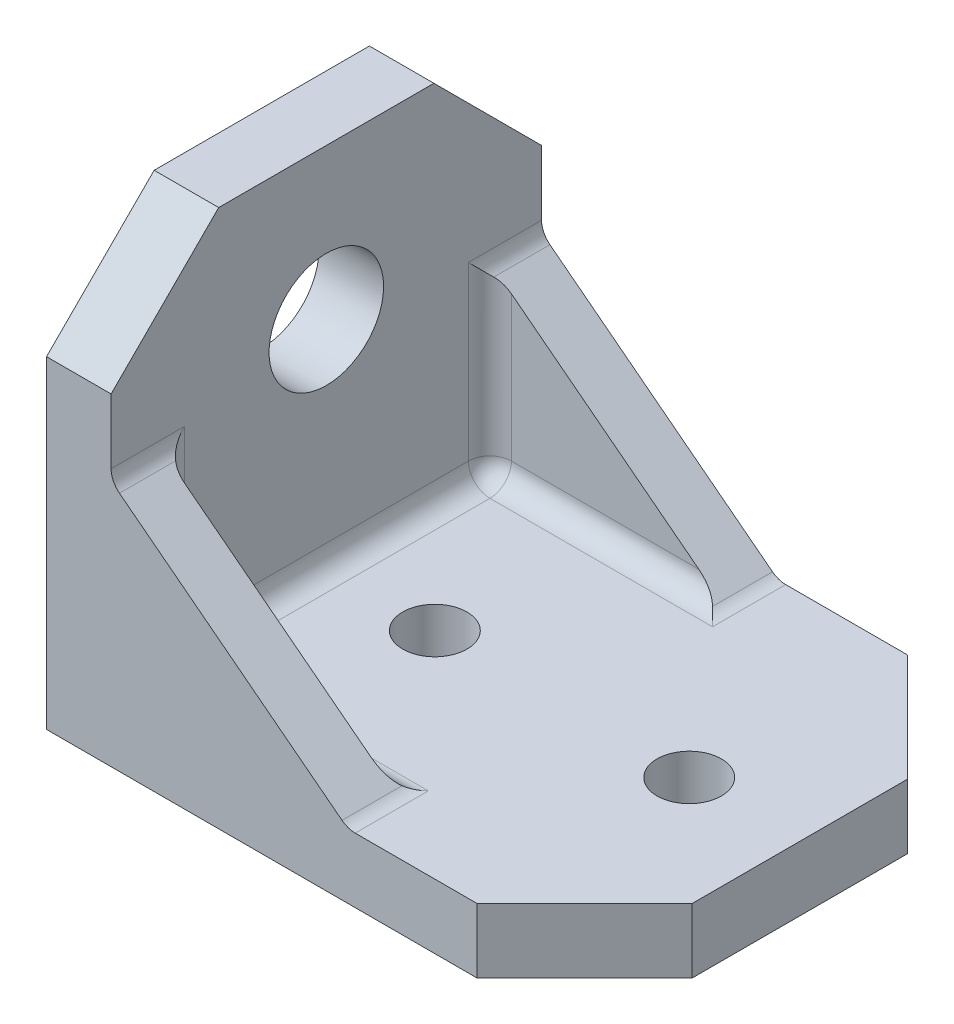
SolidWorks part; units mm, degrees
material "ABS"
ref_plane "Front" through (0, 0, 0) normal (0, 0, 1) x (1, 0, 0)
ref_plane "Top" through (0, 0, 0) normal (0, 1, 0) x (1, 0, 0)
ref_plane "Right" through (0, 0, 0) normal (1, 0, 0) x (0, 0, -1)
ref_axis "Axis1" through (0, 0, 55) along (0, 0, -1)
sketch "Sketch1" plane through (0, 0, 0) normal (0, 0, 1) x (1, 0, 0)
  line L0 (0, 0) -> (0, 25.4)
  line L1 (0, 0) -> (31.75, 0)
  line L2 (3.81, 3.81) -> (31.75, 3.81)
  line L3 (3.81, 3.81) -> (3.81, 25.4)
  line L4 (0, 25.4) -> (3.81, 25.4)
  line L5 (31.75, 3.81) -> (31.75, 0)
  dimension "D2" = 25.4
  dimension "D3" = 31.75
  dimension "D1" = 3.81
extrude "Boss-Extrude1" add sketch "Sketch1" along normal blind 25.4
hole_wizard "#6 Clearance Hole1" positions "Sketch2" profile "Sketch3" hole size "#6" standard "ANSI Inch" end condition through all
sketch "Sketch2" plane through (0, 3.81, 0) normal (0, 1, 0) x (1, 0, 0)
  line L0 (3.81, -12.7) -> (31.75, -12.7) construction
  line L1 (3.81, -25.4) -> (3.81, 0) construction
  line L2 (31.75, -25.4) -> (31.75, 0) construction
  line L4 (0, -25.4) -> (0, 0) construction
  point P0 (10.2108, -12.7)
  point P2 (25.2222, -12.7)
  point P12 (25.6439, -12.7)
  point P13 (11.4084, -12.7)
  dimension "D1" = 15.0114
  dimension "D2" = 10.2108
sketch "Sketch3" plane through (10.2108, 3.81, 12.7) normal (1, 0, 0) x (0, 0, 1)
  line L0 (0, 0) -> (0, 3.81)
  line L1 (0, 3.81) -> (1.8986, 3.81)
  line L2 (1.8986, 3.81) -> (1.8986, 0)
  line L5 (1.8986, 0) -> (0, 0)
  line L11 (0, -6.35) -> (0, 107.95) construction
  dimension "Thru Hole Dia." = 3.7973
  dimension "Thru Hole Depth" = 3.81
hole_wizard "1/4 Clearance Hole1" positions "Sketch4" profile "Sketch5" hole size "1/4" standard "ANSI Inch" end condition through all
sketch "Sketch4" plane through (3.81, 0, 0) normal (1, 0, 0) x (0, 0, -1)
  line L0 (-12.7, 25.4) -> (-12.7, 3.81) construction
  line L1 (-25.4, 25.4) -> (0, 25.4) construction
  line L2 (-25.4, 3.81) -> (0, 3.81) construction
  point P0 (-12.7, 16.51)
  point P10 (-12.7, 16.6994)
  dimension "D1" = 8.89
sketch "Sketch5" plane through (3.81, 16.51, 12.7) normal (0, 1, 0) x (0, 0, -1)
  line L0 (0, 0) -> (0, 3.81)
  line L1 (0, 3.81) -> (3.3782, 3.81)
  line L2 (3.3782, 3.81) -> (3.3782, 0)
  line L5 (3.3782, 0) -> (0, 0)
  line L11 (0, -6.35) -> (0, 107.95) construction
  dimension "Thru Hole Dia." = 6.7564
  dimension "Thru Hole Depth" = 3.81
sketch "Sketch6" plane through (0, 0, 25.4) normal (0, 0, 1) x (1, 0, 0)
  line L0 (3.81, 3.81) -> (17.78, 3.81)
  line L1 (31.75, 3.81) -> (3.81, 3.81) construction
  line L2 (17.78, 3.81) -> (3.81, 14.605)
  line L3 (3.81, 3.81) -> (3.81, 25.4) construction
  line L4 (3.81, 14.605) -> (3.81, 3.81)
extrude "Boss-Extrude2" add sketch "Sketch6" against normal blind 3.048
sketch "Sketch7" plane through (0, 0, 0) normal (0, 0, -1) x (-1, 0, 0)
  line L0 (-3.81, 3.81) -> (-17.78, 3.81)
  line L1 (-31.75, 3.81) -> (-3.81, 3.81) construction
  line L2 (-17.78, 3.81) -> (-3.81, 14.605)
  line L3 (-3.81, 3.81) -> (-3.81, 25.4) construction
  line L4 (-3.81, 14.605) -> (-3.81, 3.81)
extrude "Boss-Extrude3" add sketch "Sketch7" against normal blind 3.048
fillet "Fillet1" radius 1.27 9 edges at (17.78, 3.81, 23.876) (3.81, 14.605, 23.876) (3.81, 14.605, 1.524) (17.78, 3.81, 1.524) (10.795, 3.81, 22.352) (3.81, 9.2075, 22.352) (10.795, 3.81, 3.048) (3.81, 9.2075, 3.048) (3.81, 3.81, 12.7)
chamfer "Chamfer1" distance 6.35 angle 45 4 edges at (1.905, 25.4, 25.4) (1.905, 25.4, 0) (31.75, 1.905, 25.4) (31.75, 1.905, 0)
